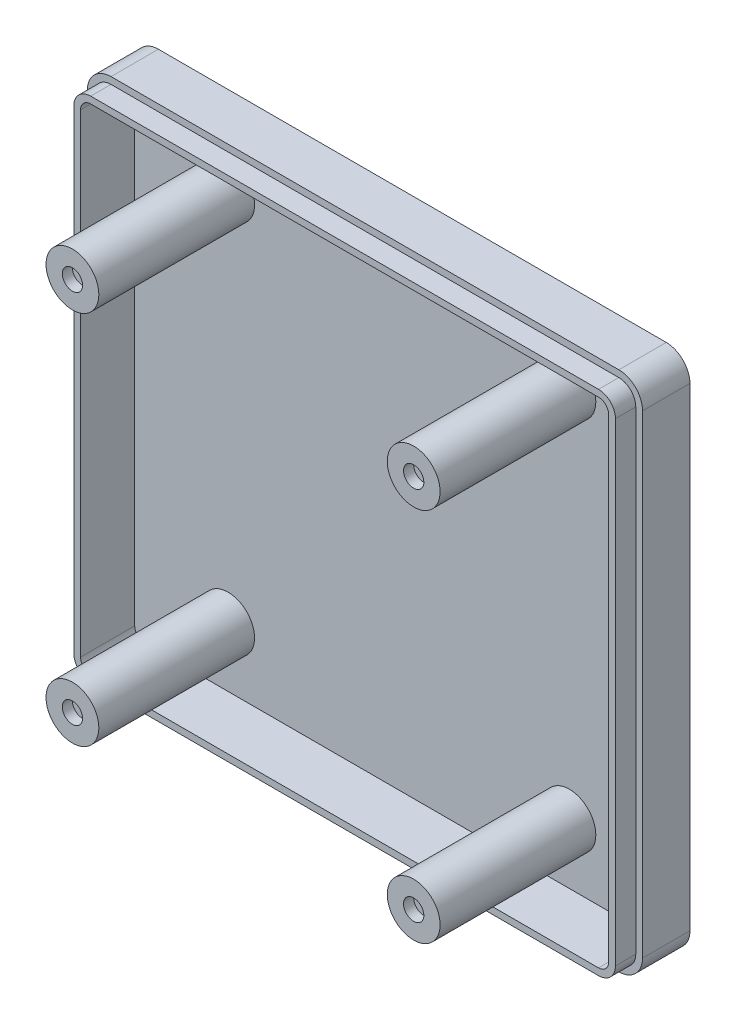
SolidWorks part; units mm, degrees
ref_plane "Plan de face" through (0, 0, 0) normal (0, 0, 1) x (1, 0, 0)
ref_plane "Plan de dessus" through (0, 0, 0) normal (0, 1, 0) x (1, 0, 0)
ref_plane "Plan de droite" through (0, 0, 0) normal (1, 0, 0) x (0, 0, -1)
sketch "Esquisse1" plane through (0, 0, 0) normal (0, 0, 1) x (1, 0, 0)
  line L0 (39.2678, -36.7678) -> (-39.2678, 36.7678) construction
  line L1 (-37.5, 37.5) -> (37.5, 37.5)
  line L2 (-40, 35) -> (-40, -35)
  line L3 (-37.5, -37.5) -> (37.5, -37.5)
  line L4 (40, 35) -> (40, -35)
  arc A0 (-37.5, 37.5) -> (-40, 35) centre (-37.5, 35) ccw
  arc A1 (40, 35) -> (37.5, 37.5) centre (37.5, 35) ccw
  arc A2 (-40, -35) -> (-37.5, -37.5) centre (-37.5, -35) ccw
  arc A3 (37.5, -37.5) -> (40, -35) centre (37.5, -35) ccw
  dimension "D3" = 5
  dimension "D4" = 5
  dimension "D5" = 5
  dimension "D6" = 5
  dimension "D1" = 80
  dimension "D2" = 75
extrude "Extru.-Mince1" add sketch "Esquisse1" along normal blind 10 thin thin type mid plane wall 2
extrude "Boss.-Extru.1" add sketch "Esquisse1<2>" along normal blind 2
sketch "Esquisse1<2>" plane through (0, 0, 0) normal (0, 0, 1) x (1, 0, 0) same geometry as "Esquisse1"
sketch "Esquisse2" plane through (0, 0, 10) normal (0, 0, 1) x (1, 0, 0)
  line L0 (-41, 35) -> (-41, -35) construction
  line L1 (-37.5, 37.5) -> (37.5, 37.5)
  line L2 (-40, 35) -> (-40, -35)
  line L3 (-37.5, -37.5) -> (37.5, -37.5)
  line L4 (40, 35) -> (40, -35)
  line L5 (41, -35) -> (41, 35) construction
  line L6 (37.5, 38.5) -> (-37.5, 38.5) construction
  line L7 (-37.5, -38.5) -> (37.5, -38.5) construction
  arc A0 (-37.5, 37.5) -> (-40, 35) centre (-37.5, 35) ccw
  arc A1 (40, 35) -> (37.5, 37.5) centre (37.5, 35) ccw
  arc A2 (-40, -35) -> (-37.5, -37.5) centre (-37.5, -35) ccw
  arc A3 (37.5, -37.5) -> (40, -35) centre (37.5, -35) ccw
  dimension "D5" = 5
  dimension "D6" = 5
  dimension "D7" = 5
  dimension "D8" = 5
  dimension "D1" = 1
  dimension "D2" = 1
  dimension "D3" = 1
  dimension "D4" = 1
extrude "Enlèv. mat.-Extru.1" cut sketch "Esquisse2" against normal blind 3 flip side to cut
sketch "Esquisse3" plane through (0, 0, 2) normal (0, 0, 1) x (1, 0, 0)
  line L0 (37.5, 37.5) -> (-37.5, 37.5) construction
  line L1 (-37.5, -37.5) -> (37.5, -37.5) construction
  line L2 (40, -35) -> (40, 35) construction
  line L3 (-40, 35) -> (-40, -35) construction
  line L4 (-40, 35) -> (-40, -35) construction
  circle A0 centre (-25.2, 27.7) radius 3.9
  circle A1 centre (25.2, 27.7) radius 3.9
  circle A2 centre (-25.2, -27.7) radius 3.9
  circle A3 centre (25.2, -27.7) radius 3.9
  dimension "D1" = 7.8
  dimension "D2" = 7.8
  dimension "D3" = 7.8
  dimension "D4" = 7.8
  dimension "D13" = 50.4
  dimension "D5" = 9.8
  dimension "D6" = 9.8
  dimension "D7" = 9.8
  dimension "D8" = 9.8
  dimension "D9" = 14.8
  dimension "D10" = 14.8
  dimension "D11" = 14.8
  dimension "D12" = 14.8
  dimension "D14" = 55.4
  dimension "D15" = 55.4
  dimension "D16" = 50.4
extrude "Boss.-Extru.2" add sketch "Esquisse3" along normal blind 23
sketch "Esquisse6" plane through (0, 0, 2) normal (0, 0, 1) x (1, 0, 0)
sketch "Esquisse9" plane through (0, 0, 25) normal (0, 0, 1) x (1, 0, 0)
  circle A1 centre (-25.2, 27.7) radius 1.5
  circle A2 centre (25.2, 27.7) radius 1.5
  circle A3 centre (-25.2, -27.7) radius 1.5
  circle A4 centre (25.2, -27.7) radius 1.5
  dimension "D1" = 3
  dimension "D2" = 3
  dimension "D3" = 3
  dimension "D4" = 3
extrude "Enlèv. mat.-Extru.2" cut sketch "Esquisse9" against normal blind 1.5
sketch "Esquisse12" plane through (0, 0, 0) normal (0, 0, -1) x (-1, 0, 0)
  circle A0 centre (24.9, 27.4) radius 1.5
  circle A1 centre (-24.9, 27.4) radius 1.5
  circle A2 centre (-24.9, -27.4) radius 1.5
  circle A3 centre (24.9, -27.4) radius 1.5
  dimension "D1" = 3
extrude "Enlèv. mat.-Extru.3" cut sketch "Esquisse12" against normal blind 21
